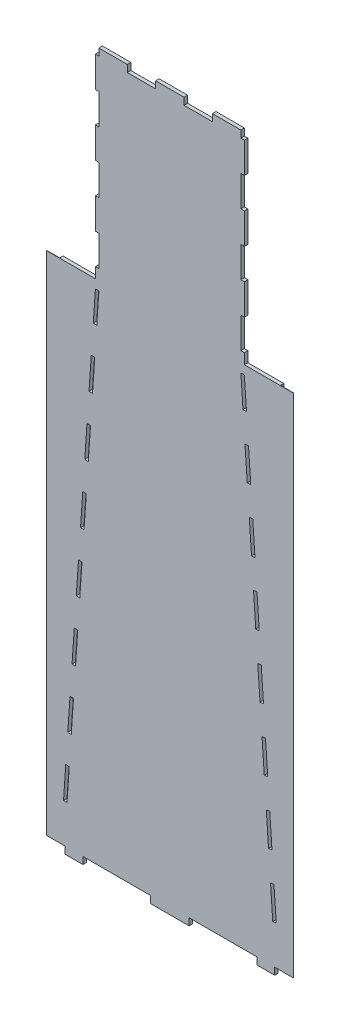
SolidWorks part; units mm, degrees
material "A-Glass Fiber"
ref_plane "Front Plane" through (0, 0, 0) normal (0, 0, 1) x (1, 0, 0)
ref_plane "Top Plane" through (0, 0, 0) normal (0, 1, 0) x (1, 0, 0)
ref_plane "Right Plane" through (0, 0, 0) normal (1, 0, 0) x (0, 0, -1)
sketch "Sketch1" plane through (0, 0, 0) normal (0, 0, 1) x (1, 0, 0)
  line L0 (-215.8818, 2072.64) -> (-215.8818, 1463.04) construction
  line L1 (308.2661, 132.944) -> (301.7555, 226.6808) construction
  line L2 (-303.52, 0) -> (252, 0) construction
  line L3 (-215.8818, 2072.64) -> (215.8818, 2072.64) construction
  line L4 (301.7555, 226.6808) -> (291.6378, 225.9781) construction
  line L5 (-205.7153, 2072.64) -> (-123.444, 2072.64)
  line L6 (-123.444, 2052.32) -> (-123.444, 2072.64)
  line L7 (-123.444, 2052.32) -> (-123.444, 2072.64)
  line L8 (-41.1356, 2072.64) -> (-41.1356, 2052.32)
  line L9 (-41.1356, 2072.64) -> (41.1356, 2072.64)
  line L10 (0, 2072.64) -> (0, 0) construction
  line L11 (291.6378, 225.9781) -> (298.1484, 132.2412) construction
  line L12 (-252, 20.32) -> (252, 20.32)
  line L13 (298.1484, 132.2412) -> (308.2661, 132.944) construction
  line L14 (289.4357, 404.0535) -> (279.318, 403.3508) construction
  line L15 (279.318, 403.3508) -> (285.8305, 309.5874) construction
  line L16 (285.8305, 309.5874) -> (295.9482, 310.2901) construction
  line L17 (-205.7153, 2072.64) -> (-123.444, 2072.64) construction
  line L18 (-205.7153, 2072.64) -> (-205.7153, 1963.42)
  line L19 (-205.7153, 1963.42) -> (-215.8818, 1963.42)
  line L20 (-215.8818, 2052.32) -> (-215.8818, 1963.42)
  line L21 (-205.7153, 1963.42) -> (-215.8818, 1963.42)
  line L23 (-205.7153, 1874.52) -> (-215.8818, 1874.52)
  line L26 (295.9482, 310.2901) -> (289.4357, 404.0535) construction
  line L28 (205.7153, 1696.72) -> (215.8753, 1696.72)
  line L29 (215.8753, 1696.72) -> (215.8753, 1607.82)
  line L30 (205.7153, 1696.72) -> (215.8753, 1696.72)
  line L31 (205.7153, 1607.82) -> (215.8753, 1607.82)
  line L32 (283.6303, 487.6362) -> (277.1159, 581.4262) construction
  line L33 (205.7153, 1607.82) -> (215.8753, 1607.82)
  line L34 (-205.7153, 1518.92) -> (215.8818, 1518.92)
  line L35 (205.7153, 1785.62) -> (215.8818, 1785.62)
  line L36 (-205.7153, 1518.92) -> (215.8818, 1518.92)
  line L37 (-215.8818, 1463.04) -> (-205.7153, 1463.04)
  line L38 (277.1159, 581.4262) -> (266.9983, 580.7234) construction
  line L39 (-215.8818, 1463.04) -> (-205.7153, 1463.04) construction
  line L40 (-205.7153, 1463.04) -> (-205.7153, 2072.64)
  line L41 (266.9983, 580.7234) -> (273.5126, 486.9335) construction
  line L42 (273.5126, 486.9335) -> (283.6303, 487.6362) construction
  line L43 (264.7962, 758.7989) -> (254.6785, 758.0961) construction
  line L44 (215.8818, 1463.04) -> (205.7153, 1463.04) construction
  line L45 (254.6785, 758.0961) -> (261.1947, 664.2796) construction
  line L46 (261.1947, 664.2796) -> (271.3124, 664.9824) construction
  line L47 (271.3124, 664.9824) -> (264.7962, 758.7989) construction
  line L48 (252.4764, 936.1715) -> (242.3588, 935.4688) construction
  line L50 (242.3588, 935.4688) -> (248.8768, 841.6258) construction
  line L52 (248.8768, 841.6258) -> (258.9945, 842.3285) construction
  line L53 (258.9945, 842.3285) -> (252.4764, 936.1715) construction
  line L54 (240.1567, 1113.5442) -> (230.039, 1112.8414) construction
  line L55 (230.039, 1112.8414) -> (236.5589, 1018.9719) construction
  line L56 (236.5589, 1018.9719) -> (246.6766, 1019.6747) construction
  line L57 (246.6766, 1019.6747) -> (240.1567, 1113.5442) construction
  line L58 (227.8369, 1290.9169) -> (217.7192, 1290.2141) construction
  line L59 (217.7192, 1290.2141) -> (224.241, 1196.3181) construction
  line L60 (224.241, 1196.3181) -> (234.3587, 1197.0208) construction
  line L61 (234.3587, 1197.0208) -> (227.8369, 1290.9169) construction
  line L62 (205.7153, 1463.04) -> (211.9231, 1373.6642) construction
  line L63 (211.9231, 1373.6642) -> (222.0407, 1374.3669) construction
  line L64 (222.0407, 1374.3669) -> (215.8818, 1463.04) construction
  line L65 (215.8818, 1463.04) -> (205.7153, 1463.04) construction
  line L66 (-211.9231, 1373.6642) -> (-205.7153, 1463.04) construction
  line L67 (252, 0) -> (303.52, 0) construction
  line L68 (-205.7153, 1463.04) -> (-215.8818, 1463.04) construction
  line L69 (-215.8818, 1463.04) -> (-222.0407, 1374.3669) construction
  line L70 (-252, 20.32) -> (-252, 0)
  line L71 (-222.0407, 1374.3669) -> (-211.9231, 1373.6642) construction
  line L72 (-217.7192, 1290.2141) -> (-227.8369, 1290.9169) construction
  line L73 (-227.8369, 1290.9169) -> (-234.3587, 1197.0208) construction
  line L74 (-234.3587, 1197.0208) -> (-224.241, 1196.3181) construction
  line L75 (-224.241, 1196.3181) -> (-217.7192, 1290.2141) construction
  line L76 (-230.039, 1112.8414) -> (-240.1567, 1113.5442) construction
  line L77 (-240.1567, 1113.5442) -> (-246.6766, 1019.6747) construction
  line L79 (-246.6766, 1019.6747) -> (-236.5589, 1018.9719) construction
  line L80 (-236.5589, 1018.9719) -> (-230.039, 1112.8414) construction
  line L81 (-242.3588, 935.4688) -> (-252.4764, 936.1715) construction
  line L82 (205.7153, 2072.64) -> (123.444, 2072.64) construction
  line L86 (-205.7153, 2052.32) -> (-215.8818, 2052.32)
  line L89 (-252.4764, 936.1715) -> (-258.9945, 842.3285) construction
  line L90 (215.8818, 2072.64) -> (215.8818, 1463.04) construction
  line L91 (-215.8818, 2052.32) -> (-205.7153, 2052.32)
  line L92 (215.8818, 2052.32) -> (205.7153, 2052.32)
  line L94 (205.7153, 2052.32) -> (-215.8818, 2052.32)
  line L98 (-258.9945, 842.3285) -> (-248.8768, 841.6258) construction
  line L99 (-248.8768, 841.6258) -> (-242.3588, 935.4688) construction
  line L101 (-254.6785, 758.0961) -> (-264.7962, 758.7989) construction
  line L102 (-264.7962, 758.7989) -> (-271.3124, 664.9824) construction
  line L104 (-271.3124, 664.9824) -> (-261.1947, 664.2796) construction
  line L105 (-261.1947, 664.2796) -> (-254.6785, 758.0961) construction
  line L106 (-277.1159, 581.4262) -> (-283.6303, 487.6362) construction
  line L107 (-283.6303, 487.6362) -> (-273.5126, 486.9335) construction
  line L108 (252, 20.32) -> (252, 0)
  line L109 (-273.5126, 486.9335) -> (-266.9983, 580.7234) construction
  line L111 (-266.9983, 580.7234) -> (-277.1159, 581.4262) construction
  line L112 (-279.318, 403.3508) -> (-289.4357, 404.0535) construction
  line L113 (-289.4357, 404.0535) -> (-295.9482, 310.2901) construction
  line L114 (-295.9482, 310.2901) -> (-285.8305, 309.5874) construction
  line L116 (-285.8305, 309.5874) -> (-279.318, 403.3508) construction
  line L117 (-301.7555, 226.6808) -> (-308.2661, 132.944) construction
  line L120 (-308.2661, 132.944) -> (-298.1484, 132.2412) construction
  line L121 (-298.1484, 132.2412) -> (-291.6378, 225.9781) construction
  line L124 (-291.6378, 225.9781) -> (-301.7555, 226.6808) construction
  line L125 (308.2661, 132.944) -> (301.7555, 226.6808)
  line L127 (301.7555, 226.6808) -> (291.6378, 225.9781)
  line L128 (205.7153, 1463.04) -> (205.7153, 2072.64)
  line L129 (215.8818, 1463.04) -> (205.7153, 1463.04)
  line L130 (205.7153, 1518.92) -> (-215.8818, 1518.92)
  line L131 (-205.7153, 1518.92) -> (-215.8818, 1518.92)
  line L132 (205.7153, 1518.92) -> (-215.8818, 1518.92)
  line L133 (-205.7153, 1607.82) -> (-215.8753, 1607.82)
  line L134 (291.6378, 225.9781) -> (298.1484, 132.2412)
  line L135 (-205.7153, 1607.82) -> (-215.8753, 1607.82)
  line L136 (-205.7153, 1696.72) -> (-215.8753, 1696.72)
  line L137 (-215.8753, 1696.72) -> (-215.8753, 1607.82)
  line L138 (-205.7153, 1696.72) -> (-215.8753, 1696.72)
  line L143 (-215.8818, 1518.92) -> (-215.8818, 1463.04)
  line L145 (205.7153, 1963.42) -> (215.8818, 1963.42)
  line L146 (215.8818, 2052.32) -> (215.8818, 1963.42)
  line L147 (205.7153, 1963.42) -> (215.8818, 1963.42)
  line L148 (205.7153, 2072.64) -> (205.7153, 1963.42)
  line L149 (41.1356, 2072.64) -> (41.1356, 2052.32)
  line L150 (123.444, 2052.32) -> (123.444, 2072.64)
  line L151 (123.444, 2052.32) -> (123.444, 2072.64)
  line L152 (205.7153, 2072.64) -> (123.444, 2072.64)
  line L153 (298.1484, 132.2412) -> (308.2661, 132.944)
  line L154 (205.7153, 1518.92) -> (215.8818, 1518.92)
  line L155 (215.8818, 1518.92) -> (215.8818, 1463.04)
  line L156 (-205.7153, 1785.62) -> (-215.8818, 1785.62)
  line L165 (-215.8818, 1874.52) -> (-215.8818, 1785.62)
  line L166 (215.8818, 1874.52) -> (215.8818, 1785.62)
  line L167 (205.7153, 1874.52) -> (215.8818, 1874.52)
  line L168 (215.8818, 1488.44) -> (358.1218, 1488.44)
  line L169 (-55.8292, 20.32) -> (55.8292, 20.32)
  line L170 (-55.8292, 20.32) -> (-55.8292, 0)
  line L171 (-55.8292, 0) -> (55.8292, 0)
  line L172 (55.8292, 20.32) -> (55.8292, 0)
  line L173 (358.1218, 1488.44) -> (358.1218, 20.32)
  line L175 (-215.8818, 1488.44) -> (-358.1218, 1488.44)
  line L176 (-358.1218, 1488.44) -> (-358.1218, 20.32)
  line L178 (289.4357, 404.0535) -> (279.318, 403.3508)
  line L179 (279.318, 403.3508) -> (285.8305, 309.5874)
  line L180 (-371.5407, 0) -> (-280.9748, 0) construction
  line L181 (-358.1218, 20.32) -> (-303.52, 20.32)
  line L184 (-303.52, 20.32) -> (-303.52, 0)
  line L185 (280.9748, 0) -> (371.5407, 0) construction
  line L186 (-303.52, 0) -> (-252, 0)
  line L187 (-303.52, 0) -> (-303.52, 20.32)
  line L189 (-252, 0) -> (-252, 20.32)
  line L190 (358.1218, 20.32) -> (303.52, 20.32)
  line L193 (303.52, 20.32) -> (303.52, 0)
  line L194 (285.8305, 309.5874) -> (295.9482, 310.2901)
  line L195 (303.52, 0) -> (252, 0)
  line L196 (303.52, 0) -> (303.52, 20.32)
  line L198 (252, 0) -> (252, 20.32)
  line L199 (295.9482, 310.2901) -> (289.4357, 404.0535)
  line L200 (283.6303, 487.6362) -> (277.1159, 581.4262)
  line L201 (277.1159, 581.4262) -> (266.9983, 580.7234)
  line L202 (266.9983, 580.7234) -> (273.5126, 486.9335)
  line L203 (273.5126, 486.9335) -> (283.6303, 487.6362)
  line L204 (264.7962, 758.7989) -> (254.6785, 758.0961)
  line L205 (254.6785, 758.0961) -> (261.1947, 664.2796)
  line L206 (261.1947, 664.2796) -> (271.3124, 664.9824)
  line L207 (271.3124, 664.9824) -> (264.7962, 758.7989)
  line L208 (252.4764, 936.1715) -> (242.3588, 935.4688)
  line L209 (242.3588, 935.4688) -> (248.8768, 841.6258)
  line L210 (248.8768, 841.6258) -> (258.9945, 842.3285)
  line L211 (258.9945, 842.3285) -> (252.4764, 936.1715)
  line L212 (240.1567, 1113.5442) -> (230.039, 1112.8414)
  line L213 (230.039, 1112.8414) -> (236.5589, 1018.9719)
  line L214 (236.5589, 1018.9719) -> (246.6766, 1019.6747)
  line L215 (246.6766, 1019.6747) -> (240.1567, 1113.5442)
  line L216 (227.8369, 1290.9169) -> (217.7192, 1290.2141)
  line L217 (217.7192, 1290.2141) -> (224.241, 1196.3181)
  line L218 (224.241, 1196.3181) -> (234.3587, 1197.0208)
  line L219 (234.3587, 1197.0208) -> (227.8369, 1290.9169)
  line L220 (205.7153, 1463.04) -> (211.9231, 1373.6642)
  line L221 (211.9231, 1373.6642) -> (222.0407, 1374.3669)
  line L222 (222.0407, 1374.3669) -> (215.8818, 1463.04)
  line L223 (215.8818, 1463.04) -> (205.7153, 1463.04)
  line L224 (-211.9231, 1373.6642) -> (-205.7153, 1463.04)
  line L225 (-205.7153, 1463.04) -> (-215.8818, 1463.04)
  line L226 (-215.8818, 1463.04) -> (-222.0407, 1374.3669)
  line L227 (-222.0407, 1374.3669) -> (-211.9231, 1373.6642)
  line L228 (-217.7192, 1290.2141) -> (-227.8369, 1290.9169)
  line L229 (-227.8369, 1290.9169) -> (-234.3587, 1197.0208)
  line L230 (-234.3587, 1197.0208) -> (-224.241, 1196.3181)
  line L231 (-224.241, 1196.3181) -> (-217.7192, 1290.2141)
  line L232 (-230.039, 1112.8414) -> (-240.1567, 1113.5442)
  line L233 (-240.1567, 1113.5442) -> (-246.6766, 1019.6747)
  line L234 (-246.6766, 1019.6747) -> (-236.5589, 1018.9719)
  line L235 (-236.5589, 1018.9719) -> (-230.039, 1112.8414)
  line L236 (-242.3588, 935.4688) -> (-252.4764, 936.1715)
  line L237 (-252.4764, 936.1715) -> (-258.9945, 842.3285)
  line L238 (-258.9945, 842.3285) -> (-248.8768, 841.6258)
  line L239 (-248.8768, 841.6258) -> (-242.3588, 935.4688)
  line L240 (-254.6785, 758.0961) -> (-264.7962, 758.7989)
  line L241 (-264.7962, 758.7989) -> (-271.3124, 664.9824)
  line L242 (-271.3124, 664.9824) -> (-261.1947, 664.2796)
  line L243 (-261.1947, 664.2796) -> (-254.6785, 758.0961)
  line L244 (-277.1159, 581.4262) -> (-283.6303, 487.6362)
  line L245 (-283.6303, 487.6362) -> (-273.5126, 486.9335)
  line L246 (-273.5126, 486.9335) -> (-266.9983, 580.7234)
  line L247 (-266.9983, 580.7234) -> (-277.1159, 581.4262)
  line L248 (-279.318, 403.3508) -> (-289.4357, 404.0535)
  line L249 (-289.4357, 404.0535) -> (-295.9482, 310.2901)
  line L250 (-295.9482, 310.2901) -> (-285.8305, 309.5874)
  line L251 (-285.8305, 309.5874) -> (-279.318, 403.3508)
  line L252 (-301.7555, 226.6808) -> (-308.2661, 132.944)
  line L253 (-308.2661, 132.944) -> (-298.1484, 132.2412)
  line L254 (-298.1484, 132.2412) -> (-291.6378, 225.9781)
  line L255 (-291.6378, 225.9781) -> (-301.7555, 226.6808)
  line L258 (358.1218, 1488.44) -> (358.1218, 20.32)
  point P11 (-252, 10.16)
  point P130 (-210.7985, 1463.04)
  point P141 (0, 20.32)
  dimension "D3" = 609.6
  dimension "D4" = 2072.64
  dimension "D5" = 20.32
  dimension "D6" = 88.9
  dimension "D7" = 20.32
  dimension "D9" = 41.1356
  dimension "D10" = 10.1665
  dimension "D11" = 205.7153
  dimension "D12" = 10.16
  dimension "D13" = 10.16
  dimension "D14" = 88.9
  dimension "D15" = 88.9
  dimension "D16" = 88.9
  dimension "D18" = 88.9
  dimension "D20" = 88.9
  dimension "D21" = 20.32
  dimension "D22" = 142.24
  dimension "D23" = 142.24
  dimension "D24" = 25.4
  dimension "D25" = 25.4
  dimension "D26" = 252
  dimension "D27" = 51.52
extrude "Boss-Extrude1" add sketch "Sketch1" along normal blind 10.16 contours L128 L130 L36 L34 L40 L12 | L130 L128 L94 L40 L34 L36 | L213 | L12 L70 | L108 L12 | L128 L31 L29 L28 | L136 L137 L133 L40 | L146 L92 L128 L145 | L40 L86 L20 L19 | L94 L6 L5 L18 | L149 L9 L8 L94 | L128 L152 L150 L94 | L131 L143 L37 L40 | L155 L154 L128 L129 | L167 L128 L35 L166 | L23 L165 L156 L40 | L172 L12 L170 | L143 L175 L176 L205 | L173 L168 L155 | L12 L172 | L170 L12 | L193 | L184 | L176 | L173 region at (-164.5796, 2062.48, 0) region at (0, 1785.62, 0) region at (-210.7985, 2007.87, 0) region at (0, 2062.48, 0) region at (-210.7985, 1830.07, 0) region at (164.5796, 2062.48, 0) region at (-210.7953, 1652.27, 0) region at (210.7985, 2007.87, 0) region at (0, 760.8845, 0) region at (-210.7985, 1490.98, 0) region at (210.7985, 1830.07, 0) region at (210.7985, 1490.98, 0) region at (210.7953, 1652.27, 0) region at (0, 10.16, 0)
sketch "Sketch2" plane through (0, 0, 0) normal (0, 1, 0) x (1, 0, 0)
  line L1 (358.1218, 0) -> (320.0218, 0)
  line L2 (358.1218, 0) -> (358.1218, -9.5)
  line L3 (358.1218, -9.5) -> (320.0218, -9.5)
  line L4 (320.0218, 0) -> (320.0218, -9.5)
  line L5 (0, 0) -> (0, -34.3067) construction
  line L6 (0, -5.588) -> (0, 5.588) construction
  line L7 (-320.0218, 0) -> (-320.0218, -9.5)
  line L8 (-358.1218, -9.5) -> (-320.0218, -9.5)
  line L9 (-358.1218, 0) -> (-358.1218, -9.5)
  line L10 (-358.1218, 0) -> (-320.0218, 0)
  dimension "D1" = 38.1
  dimension "D2" = 9.5
extrude "Cut-Extrude1" cut sketch "Sketch2" along normal blind 2540
